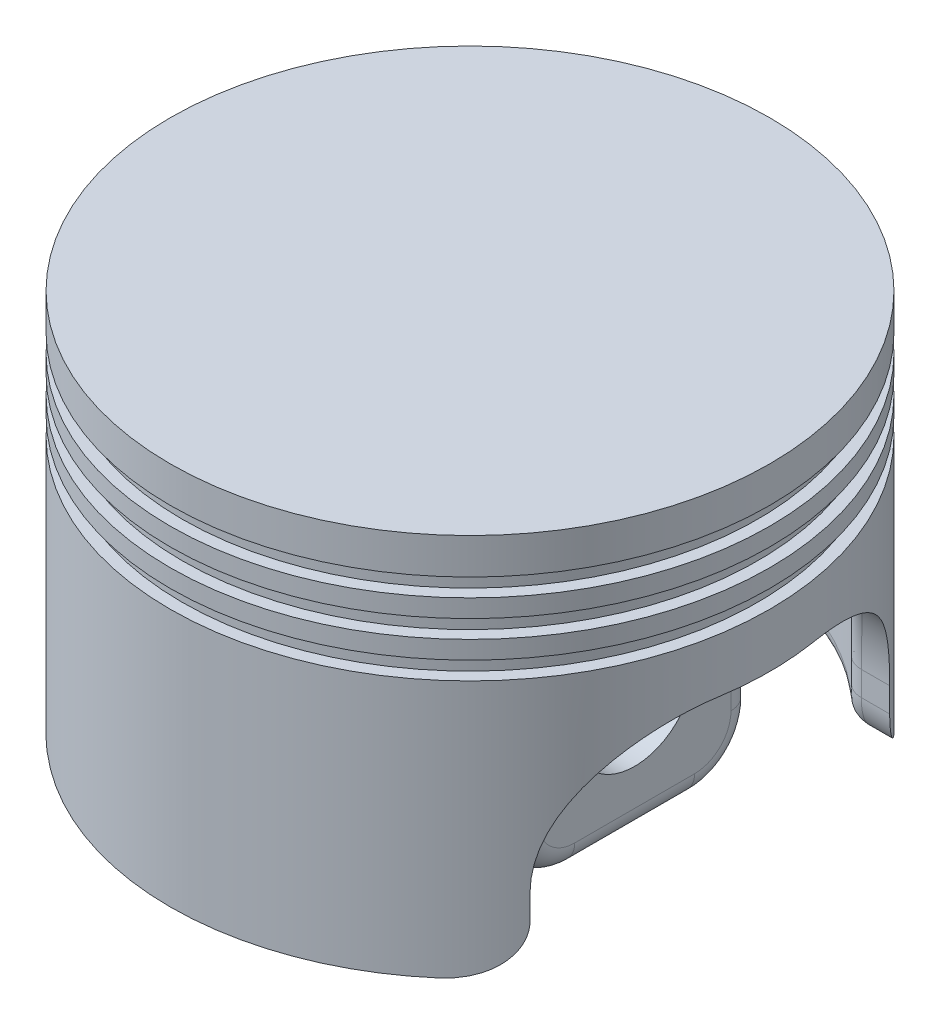
SolidWorks part; units mm, degrees
ref_plane "Front Plane" through (0, 0, 0) normal (0, 0, 1) x (1, 0, 0)
ref_plane "Top Plane" through (0, 0, 0) normal (0, 1, 0) x (1, 0, 0)
ref_plane "Right Plane" through (0, 0, 0) normal (1, 0, 0) x (0, 0, -1)
sketch "Sketch1" plane through (0, 0, 0) normal (1, 0, 0) x (0, 0, -1)
  line L0 (0, 0) -> (63.5, 0)
  line L1 (63.5, 0) -> (63.5, -81.28)
  line L2 (63.5, -81.28) -> (57.15, -81.28)
  line L3 (57.15, -81.28) -> (57.15, -19)
  line L4 (57.15, -19) -> (0, -19)
  line L5 (0, -19) -> (0, 0)
  dimension "D1" = 63.5
  dimension "D2" = 81.28
  dimension "D3" = 6.35
  dimension "D4" = 19
revolve "Revolve1" add sketch "Sketch1" angle 360 about L5
sketch "Sketch4" plane through (0, 0, 0) normal (0, 0, 1) x (1, 0, 0)
  line L0 (63.5, -7.62) -> (60.96, -7.62)
  line L1 (60.96, -7.62) -> (60.96, -11.43)
  line L2 (60.96, -11.43) -> (63.5, -11.43)
  line L3 (63.5, -11.43) -> (63.5, -7.62)
  line L4 (63.5, 0) -> (-63.5, 0) construction
  dimension "D1" = 7.62
  dimension "D2" = 3.81
  dimension "D3" = 2.54
  dimension "D4" = 63.5
ref_axis "Axis2" through (0, 4.064, 0) along (0, -1, 0)
revolve "Cut-Revolve2" cut sketch "Sketch4" angle 360 about axis through (0, 4.064, 0) along (0, -1, 0)
pattern_linear "LPattern2" count 3 spacing 7.62 along (0, -1, 0) of "Cut-Revolve2"
sketch "Sketch5" plane through (0, 0, 0) normal (1, 0, 0) x (0, 0, -1)
  line L0 (0, 4.064) -> (0, -85.344) construction
  line L1 (38.1, -38.1) -> (-38.1, -38.1)
  line L2 (38.1, -38.1) -> (38.1, -81.28)
  line L3 (38.1, -81.28) -> (-38.1, -81.28)
  line L4 (-38.1, -38.1) -> (-38.1, -81.28)
  line L5 (38.1, -38.1) -> (-38.1, -81.28) construction
  line L6 (38.1, -81.28) -> (-38.1, -38.1) construction
  line L7 (-57.15, -81.28) -> (57.15, -81.28) construction
  line L8 (63.5, 0) -> (-63.5, 0) construction
  point P0 (0, -59.69)
  dimension "D1" = 76.2
  dimension "D2" = 38.1
extrude "Cut-Extrude2" cut sketch "Sketch5" against normal mid plane 4572
fillet "Fillet1" radius 28 4 edges at (-46.6985, -38.1, 38.1) (-46.6985, -38.1, -38.1) (46.6985, -38.1, -38.1) (46.6985, -38.1, 38.1)
sketch "Sketch6" plane through (0, -19, 0) normal (0, -1, 0) x (1, 0, 0)
  line L1 (-15.88, -25.4) -> (-34.88, -25.4)
  line L2 (-15.88, -25.4) -> (-15.88, 25.4)
  line L3 (-15.88, 25.4) -> (-34.88, 25.4)
  line L4 (-34.88, -25.4) -> (-34.88, 25.4)
  line L5 (-15.88, -25.4) -> (-34.88, 25.4) construction
  line L6 (-15.88, 25.4) -> (-34.88, -25.4) construction
  point P0 (-25.38, 0)
  dimension "D1" = 19
  dimension "D2" = 15.88
  dimension "D3" = 50.8
extrude "Boss-Extrude1" add sketch "Sketch6" along normal blind 63.5
mirror "Mirror1" about plane through (0, 0, 0) normal (1, 0, 0) of "Boss-Extrude1"
sketch "Sketch7" plane through (-34.88, 0, 0) normal (-1, 0, 0) x (0, 0, 1)
  line L0 (0, 4.064) -> (0, -85.344) construction
  line L1 (25.4, -82.5) -> (-25.4, -82.5) construction
  circle A0 centre (0, -57.1) radius 12.7
  dimension "D1" = 25.4
  dimension "D2" = 25.4
extrude "Cut-Extrude3" cut sketch "Sketch7" against normal blind 116.5
fillet "Fillet2" radius 12.7 4 edges at (25.38, -82.5, 25.4) (25.38, -82.5, -25.4) (-25.38, -82.5, -25.4) (-25.38, -82.5, 25.4)
fillet "Fillet3" radius 10 4 edges at (46.6985, -81.28, 38.1) (46.6985, -81.28, -38.1) (-46.6985, -81.28, -38.1) (-46.6985, -81.28, 38.1)
fillet "Fillet4" radius 5 20 edges at (15.88, -44.4, -25.4) (15.88, -78.7803, -21.6803) (15.88, -44.4, 25.4) (15.88, -78.7803, 21.6803) (34.88, -44.4, 25.4) (34.88, -78.7803, 21.6803) (34.88, -44.4, -25.4) (34.88, -78.7803, -21.6803) (-15.88, -44.4, -25.4) (-15.88, -78.7803, -21.6803) (-15.88, -44.4, 25.4) (-15.88, -78.7803, 21.6803) (-34.88, -44.4, 25.4) (-34.88, -78.7803, 21.6803) (-34.88, -44.4, -25.4) (-34.88, -78.7803, -21.6803) (15.88, -82.5, 0) (34.88, -82.5, 0) (-15.88, -82.5, 0) (-34.88, -82.5, 0)
fillet "Fillet5" radius 5 16 edges at (41.3657, -76.2692, 39.4335) (42.5971, -68.69, 38.1) (50.4318, -43.6881, 26.8841) (57.15, -38.1, 0) (46.055, -51.2516, -33.8387) (42.5971, -68.69, -38.1) (40.0022, -78.1316, -40.816) (0, -81.28, -57.15) (-41.3657, -76.2692, -39.4335) (-42.5971, -68.69, -38.1) (-50.4318, -43.6881, -26.8841) (-57.15, -38.1, 0) (-46.055, -51.2516, 33.8387) (-42.5971, -68.69, 38.1) (-40.0022, -78.1316, 40.816) (0, -81.28, 57.15)
